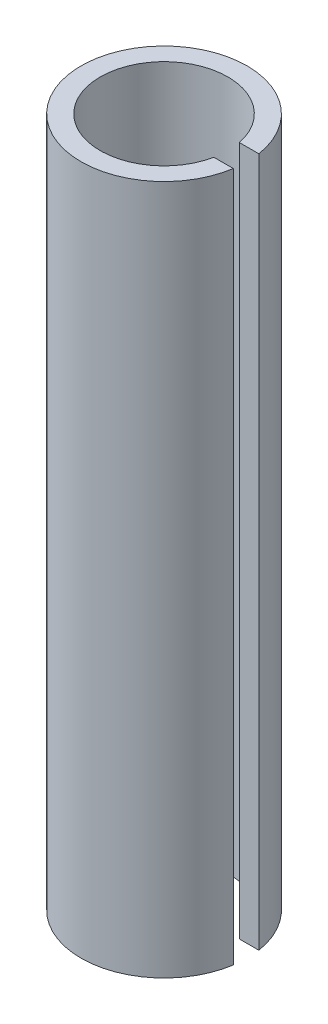
SolidWorks part; units mm, degrees
ref_plane "Front Plane" through (0, 0, 0) normal (0, 0, 1) x (1, 0, 0)
ref_plane "Top Plane" through (0, 0, 0) normal (0, 1, 0) x (1, 0, 0)
ref_plane "Right Plane" through (0, 0, 0) normal (1, 0, 0) x (0, 0, -1)
sketch "Sketch1" plane through (0, 0, 0) normal (0, 1, 0) x (1, 0, 0)
  line L0 (2.4495, 0.5) -> (3.2113, 0.5)
  line L1 (2.4495, -0.5) -> (3.2113, -0.5)
  line L2 (0, 0) -> (3.25, 0) construction
  circle A0 centre (0, 0) radius 3.25
  circle A1 centre (0, 0) radius 2.5
  dimension "D1" = 5
  dimension "D2" = 6.5
  dimension "D3" = 1
  dimension "D4" = 0.5
extrude "Boss-Extrude1" add sketch "Sketch1" along normal blind 27 contours A1 L0 A0 L1 region at (-2.5917, 0, 0)
